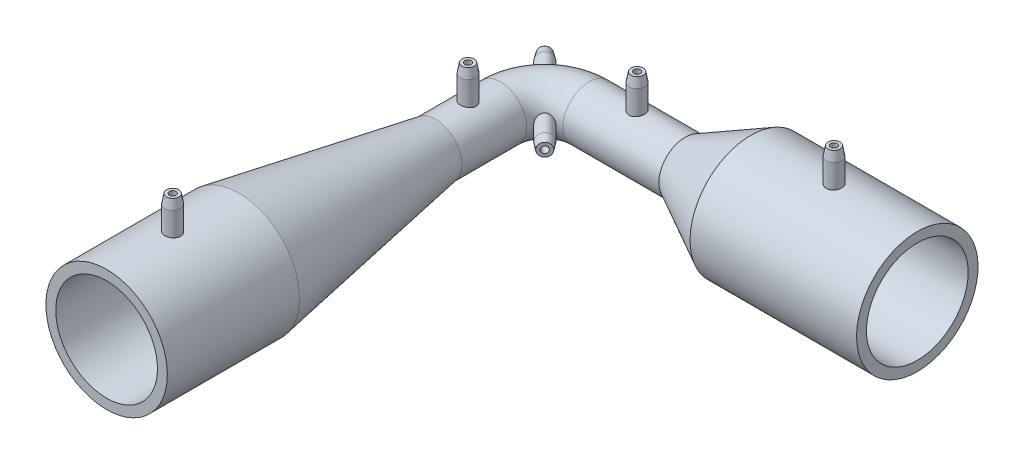
SolidWorks part; units mm, degrees
ref_plane "Front Plane" through (0, 0, 0) normal (0, 0, 1) x (1, 0, 0)
ref_plane "Top Plane" through (0, 0, 0) normal (0, 1, 0) x (1, 0, 0)
ref_plane "Right Plane" through (0, 0, 0) normal (1, 0, 0) x (0, 0, -1)
sketch "Sketch3" [suppressed] plane through (0, 0, 0) normal (0, 0, 1) x (1, 0, 0)
  circle A0 centre (0, 0) radius 15.25
  circle A1 centre (0, 0) radius 18.25
  dimension "D1" = 31
sketch "Sketch4" plane through (0, 0, 0) normal (1, 0, 0) x (0, 0, -1)
  line L0 (0, 0) -> (40, 0)
  line L1 (40, 0) -> (100, 0)
  line L2 (100, 0) -> (120, 0)
  line L3 (120, 0) -> (136, 0)
  line L4 (0, 0) -> (0, 15.5) construction
  line L5 (0, 15.5) -> (40, 15.5)
  line L6 (40, 15.5) -> (40, 0) construction
  line L7 (40, 15.5) -> (100, 5)
  line L8 (100, 5) -> (100, 0) construction
  line L9 (100, 5) -> (120, 5)
  line L10 (120, 5) -> (120, 0) construction
  line L11 (0, 18.5) -> (40.2605, 18.5)
  line L12 (40.2605, 18.5) -> (100.2605, 8)
  line L13 (100.2605, 8) -> (120, 8)
  line L14 (120, 8) -> (120, 5)
  line L15 (0, 18.5) -> (0, 15.5)
  line L16 (20.1303, 18.5) -> (20.1303, 28.5)
  line L17 (110.1303, 8) -> (110.1303, 18)
  line L18 (0, 17) -> (34.2122, 17)
  line L19 (20.1303, 18.5) -> (20.1303, 17)
  line L20 (22.5153, 18.5) -> (22.5153, 17)
  line L21 (22.5153, 18.5) -> (22.5153, 28.5)
  line L22 (17.7453, 18.5) -> (17.7453, 17)
  line L23 (17.7453, 18.5) -> (17.7453, 28.5)
  line L24 (21.1303, 18.5) -> (21.1303, 17)
  line L25 (21.1303, 18.5) -> (21.1303, 28.5)
  line L26 (19.1303, 18.5) -> (19.1303, 17)
  line L27 (19.1303, 18.5) -> (19.1303, 28.5)
  line L28 (17.7453, 28.5) -> (22.5153, 28.5)
  line L29 (22.5153, 17) -> (17.7453, 17)
  line L30 (120, 6.5) -> (102.7146, 6.5)
  line L31 (110.1303, 8) -> (110.1303, 6.5)
  line L32 (109.1303, 8) -> (109.1303, 18)
  line L33 (109.1303, 8) -> (109.1303, 6.5)
  line L34 (111.1303, 8) -> (111.1303, 18)
  line L35 (111.1303, 8) -> (111.1303, 6.5)
  line L36 (112.5153, 8) -> (112.5153, 6.5)
  line L37 (112.5153, 8) -> (112.5153, 18)
  line L38 (107.7453, 8) -> (107.7453, 6.5)
  line L39 (107.7453, 8) -> (107.7453, 18)
  line L40 (107.7453, 18) -> (112.5153, 18)
  line L41 (112.5153, 6.5) -> (107.7453, 6.5)
  dimension "D1" = 40
  dimension "D2" = 60
  dimension "D3" = 16
  dimension "D4" = 20
  dimension "D5" = 15.5
  dimension "D6" = 5
  dimension "D8" = 10
  dimension "D9" = 10
  dimension "D7" = 3
  dimension "D10" = 2.385
  dimension "D11" = 2.385
  dimension "D12" = 1
  dimension "D13" = 1
  dimension "D14" = 1
  dimension "D15" = 1
  dimension "D16" = 2.385
  dimension "D17" = 2.385
ref_plane "Plane1" [suppressed] through (0, 0, -10) normal (0, 0, 1) x (1, 0, 0)
ref_plane "Plane2" [suppressed] through (0, 0, -40) normal (0, 0, 1) x (1, 0, 0)
ref_plane "Plane3" [suppressed] through (0, 0, -50) normal (0, 0, 1) x (1, 0, 0)
sketch "Sketch6" [suppressed] plane through (0, 0, -10) normal (0, 0, 1) x (1, 0, 0)
  circle A0 centre (0, 0) radius 15.25
  circle A1 centre (0, 0) radius 18.25
  dimension "D1" = 31
sketch "Sketch7" [suppressed] plane through (0, 0, -40) normal (0, 0, 1) x (1, 0, 0)
  circle A0 centre (0, 0) radius 10
  circle A1 centre (0, 0) radius 13
  dimension "D1" = 10
sketch "Sketch8" [suppressed] plane through (0, 0, -50) normal (0, 0, 1) x (1, 0, 0)
  circle A0 centre (0, 0) radius 10
  circle A1 centre (0, 0) radius 13
  dimension "D1" = 10
revolve "Revolve5" add sketch "Sketch4" angle 360 about L0 region at (0, 12.3913, -62.201)
sketch "Sketch13" plane through (0, 0, 0) normal (0, 1, 0) x (1, 0, 0)
  circle A0 centre (8, 120) radius 16
  circle A1 centre (8, 120) radius 13
  dimension "D1" = 32
  dimension "D2" = 26
ref_plane "Plane5" through (8, 0, 0) normal (1, 0, 0) x (0, 0, -1)
sketch "Sketch15" plane through (8, 0, 0) normal (1, 0, 0) x (0, 0, -1)
  line L0 (136, 0) -> (120, 0)
  line L1 (120, -16.7311) -> (120, 16.7311)
  circle A0 centre (128, 0) radius 8
  circle A1 centre (128, 0) radius 5
  point P10 (120, 0)
  dimension "D1" = 10
sketch "Sketch17" plane through (0, 0, -120) normal (0, 0, -1) x (-1, 0, 0)
  line L0 (-13, -15.9711) -> (-13, 15.9711) construction
  line L1 (-13.5, -15.9711) -> (-13.5, 15.9711)
  circle A0 centre (0, 0) radius 10
  circle A1 centre (0, 0) radius 13
  point P7 (-13, 0)
  dimension "D1" = 0.5
revolve "Revolve13" add sketch "Sketch17" angle 90 about L1 region at (7.7737, 0, -120) reverse direction yes
sketch "Sketch18" plane through (13.5, 0, 0) normal (1, 0, 0) x (0, 0, -1)
  line L1 (133.5, 5) -> (133.5, -5)
  line L2 (53.5, 0) -> (213.5, 0)
  circle A2 centre (133.5, 0) radius 5 construction
  circle A3 centre (133.5, 0) radius 80
  circle A4 centre (133.5, 0) radius 13
ref_plane "Plane6" through (0, 0, -133.5) normal (0, 0, 1) x (1, 0, 0)
sketch "Sketch20" plane through (0, 0, -133.5) normal (0, 0, 1) x (1, 0, 0)
  line L0 (13.5, 5) -> (43.5, 5)
  line L1 (43.5, 5) -> (63.5, 15.5)
  line L2 (63.5, 15.5) -> (113.5, 15.5)
  line L3 (13.5, 0) -> (78.5, 0) construction
  line L4 (13.5, 8) -> (42.7604, 8)
  line L5 (42.7604, 8) -> (62.7604, 18.5)
  line L6 (62.7604, 18.5) -> (113.5, 18.5)
  line L7 (13.5, 8) -> (13.5, 5)
  line L8 (113.5, 18.5) -> (113.5, 15.5)
  line L9 (28.1302, 8) -> (28.1302, 18)
  line L10 (88.1302, 18.5) -> (88.1302, 28.5)
  line L11 (13.5, 6.5) -> (38.9814, 6.5) construction
  line L12 (113.5, 17) -> (66.1564, 17) construction
  line L13 (88.1302, 18.5) -> (88.1302, 17)
  line L14 (28.1302, 8) -> (28.1302, 6.5)
  line L15 (30.5152, 8) -> (30.5152, 6.5)
  line L16 (30.5152, 8) -> (30.5152, 18)
  line L17 (25.7452, 8) -> (25.7452, 6.5)
  line L18 (25.7452, 8) -> (25.7452, 18)
  line L19 (29.1302, 8) -> (29.1302, 6.5)
  line L20 (29.1302, 8) -> (29.1302, 18)
  line L21 (27.1302, 8) -> (27.1302, 6.5)
  line L22 (27.1302, 8) -> (27.1302, 18)
  line L23 (89.1302, 18.5) -> (89.1302, 17)
  line L24 (89.1302, 18.5) -> (89.1302, 28.5)
  line L25 (87.1302, 18.5) -> (87.1302, 17)
  line L26 (87.1302, 18.5) -> (87.1302, 28.5)
  line L27 (90.4882, 18.5) -> (90.4882, 17)
  line L28 (90.4882, 18.5) -> (90.4882, 28.5)
  line L29 (85.7452, 18.5) -> (85.7452, 17)
  line L30 (85.7452, 18.5) -> (85.7452, 28.5)
  line L31 (85.7452, 28.5) -> (90.4882, 28.5)
  line L32 (85.7452, 17) -> (90.4882, 17)
  line L33 (25.7452, 18) -> (30.5152, 18)
  line L34 (25.7452, 6.5) -> (30.5152, 6.5)
  dimension "D12" = 1
  dimension "D13" = 1
  dimension "D1" = 30
  dimension "D2" = 20
  dimension "D3" = 50
  dimension "D4" = 15.5
  dimension "D6" = 10
  dimension "D7" = 10
  dimension "D5" = 3
  dimension "D8" = 2.385
  dimension "D9" = 2.385
  dimension "D10" = 1
  dimension "D11" = 1
  dimension "D14" = 2.358
  dimension "D15" = 2.385
revolve "Revolve14" add sketch "Sketch20" angle 360 about L3
revolve "Revolve15" add sketch "Sketch4<6>" angle 360 about L16 region at (0, 17.75, -21.8228) region at (0, 23.5, -21.8228)
sketch "Sketch4<6>" plane through (0, 0, 0) normal (1, 0, 0) x (0, 0, -1) same geometry as "Sketch4"
revolve "Revolve16" add sketch "Sketch4<7>" angle 360 about L17 region at (0, 7.25, -111.8228) region at (0, 13, -111.8228)
sketch "Sketch4<7>" plane through (0, 0, 0) normal (1, 0, 0) x (0, 0, -1) same geometry as "Sketch4"
revolve "Revolve17" add sketch "Sketch20<3>" angle 360 about L10 region at (89.8092, 17.75, -133.5) region at (89.8092, 23.5, -133.5)
sketch "Sketch20<3>" plane through (0, 0, -133.5) normal (0, 0, 1) x (1, 0, 0) same geometry as "Sketch20"
revolve "Revolve18" add sketch "Sketch20<4>" angle 360 about L9 region at (29.8227, 13, -133.5) region at (29.8227, 7.25, -133.5)
sketch "Sketch20<4>" plane through (0, 0, -133.5) normal (0, 0, 1) x (1, 0, 0) same geometry as "Sketch20"
chamfer "Chamfer1" distance 0.5 angle 80 1 edges at (0, 18, -112.5153) first distance on face at (0, 18, -112.5153)
chamfer "Chamfer2" distance 0.5 angle 80 1 edges at (0, 28.5, -22.5153) first distance on face at (0, 28.5, -22.5153)
chamfer "Chamfer3" distance 0.5 angle 80 1 edges at (28.1302, 18, -135.885) first distance on face at (28.1302, 18, -135.885)
chamfer "Chamfer4" distance 0.5 angle 80 1 edges at (88.1302, 28.5, -135.858) first distance on face at (88.1302, 28.5, -135.858)
sketch "Sketch23" plane through (0, 0, 0) normal (0, 1, 0) x (1, 0, 0)
  circle A0 centre (0, 20.1303) radius 1
  circle A1 centre (0, 110.1303) radius 1
  circle A2 centre (28.1302, 133.5) radius 1
  circle A3 centre (88.1302, 133.5) radius 1
extrude "Cut-Extrude1" cut sketch "Sketch23" along normal up to next
sketch "Sketch24" plane through (0, 0, 0) normal (0, 1, 0) x (1, 0, 0)
  line L0 (9.6109, 123.8891) -> (-1.7028, 135.2028)
  line L1 (-15.653, 121.2526) -> (12.2474, 149.153)
  line L2 (-5.631, 108.6471) -> (24.8529, 139.131)
  arc A0 (13.5, 125.5) -> (8, 120) centre (13.5, 120) ccw construction
  arc A1 (13.5, 141.5) -> (-8, 120) centre (13.5, 120) ccw construction
  point P10 (-1.7028, 135.2028)
  point P14 (9.6109, 123.8891)
ref_plane "Plane7" through (-57.1391, 0, -57.1391) normal (0.7071, 0, 0.7071) x (0.7071, 0, -0.7071)
ref_plane "Plane8" through (-68.4528, 0, -68.4528) normal (-0.7071, 0, -0.7071) x (0.7071, 0, -0.7071)
sketch "Sketch25" plane through (-57.1391, 0, -57.1391) normal (0.7071, 0, 0.7071) x (0.7071, 0, -0.7071)
  circle A0 centre (94.3988, 0) radius 2.385
  dimension "D1" = 4.77
extrude "Boss-Extrude2" add sketch "Sketch25" along normal blind 10 and the other way blind 2
sketch "Sketch26" plane through (-68.4528, 0, -68.4528) normal (-0.7071, 0, -0.7071) x (0.7071, 0, -0.7071)
  circle A0 centre (94.3988, 0) radius 2.385
  circle A1 centre (94.3988, 0) radius 1
  dimension "D1" = 4.77
  dimension "D2" = 2
extrude "Boss-Extrude4" add sketch "Sketch26" along normal blind 10 and the other way up to next separate body contours A0
extrude "Cut-Extrude2" cut sketch "Sketch26<3>" against normal through all and the other way through all contours A1 region at (-1.7028, 0, -135.2028)
sketch "Sketch26<3>" plane through (-68.4528, 0, -68.4528) normal (-0.7071, 0, -0.7071) x (0.7071, 0, -0.7071) same geometry as "Sketch26"
chamfer "Chamfer5" distance 0.5 angle 80 1 edges at (-10.4603, 0, -140.5874) first distance on face at (-9.481, 0, -141.5668)
chamfer "Chamfer6" [suppressed] distance 0.5 angle 80
chamfer "Chamfer7" [suppressed] distance 2 angle 45
chamfer "Chamfer8" distance 3 angle 8 1 edges at (18.3684, 0, -118.5045) first distance on face at (18.3684, 0, -118.5045)
move or copy body "Body-Convert to Mesh Body2" [suppressed] bodies to move or copy 117 118 copy no translate (0, 0, 0) parameters "D1"=0, "D2"=0, "D3"=0
equation "\"vacuum_inlet_radius\"= 15.5"
equation "\"D1@Sketch3\"=\"vacuum_inlet_radius\"*2"
equation "\"inlet_length\"= 40"
equation "\"inlet_decline_length\"= 60"
equation "\"center_radius\"= 5"
equation "\"outlet_incline_length\"= 20"
equation "\"outlet_length\"= 50"
equation "\"outlet_radius\"= \"vacuum_inlet_radius\""
equation "\"corner_in_length\"= 20"
equation "\"corner_out_length\"= 30"
equation "\"D1@Sketch4\"=\"inlet_length\""
equation "\"turn_radius\"= \"center_radius\" * 2 + 6mm"
equation "\"D3@Sketch4\"=\"turn_radius\""
equation "\"D4@Sketch4\"=\"corner_in_length\""
equation "\"D2@Sketch4\"=\"inlet_decline_length\""
equation "\"D5@Sketch4\"=\"vacuum_inlet_radius\""
equation "\"D1@Sketch6\"=\"vacuum_inlet_radius\"*2"
equation "\"D1@Sketch7\"=\"center_radius\"*2"
equation "\"D6@Sketch4\"=\"center_radius\""
equation "\"D1@Sketch8\"=\"center_radius\"*2"
equation "\"D1@Sketch13\"=\"center_radius\"*4+12mm"
equation "\"D2@Sketch13\"=\"center_radius\"*4+6mm"
equation "\"D1@Sketch15\"=\"center_radius\"*2"
equation "\"D1@Sketch20\"=\"corner_out_length\""
equation "\"D2@Sketch20\"=\"outlet_incline_length\""
equation "\"D3@Sketch20\"=\"outlet_length\""
equation "\"D4@Sketch20\"=\"outlet_radius\""
equation "\"nozzle_length\"= 10"
equation "\"D8@Sketch4\"=\"nozzle_length\""
equation "\"D9@Sketch4\"=\"nozzle_length\""
equation "\"D6@Sketch20\"=\"nozzle_length\""
equation "\"D7@Sketch20\"=\"nozzle_length\""
equation "\"D1@Sketch25\"=4.77mm"
